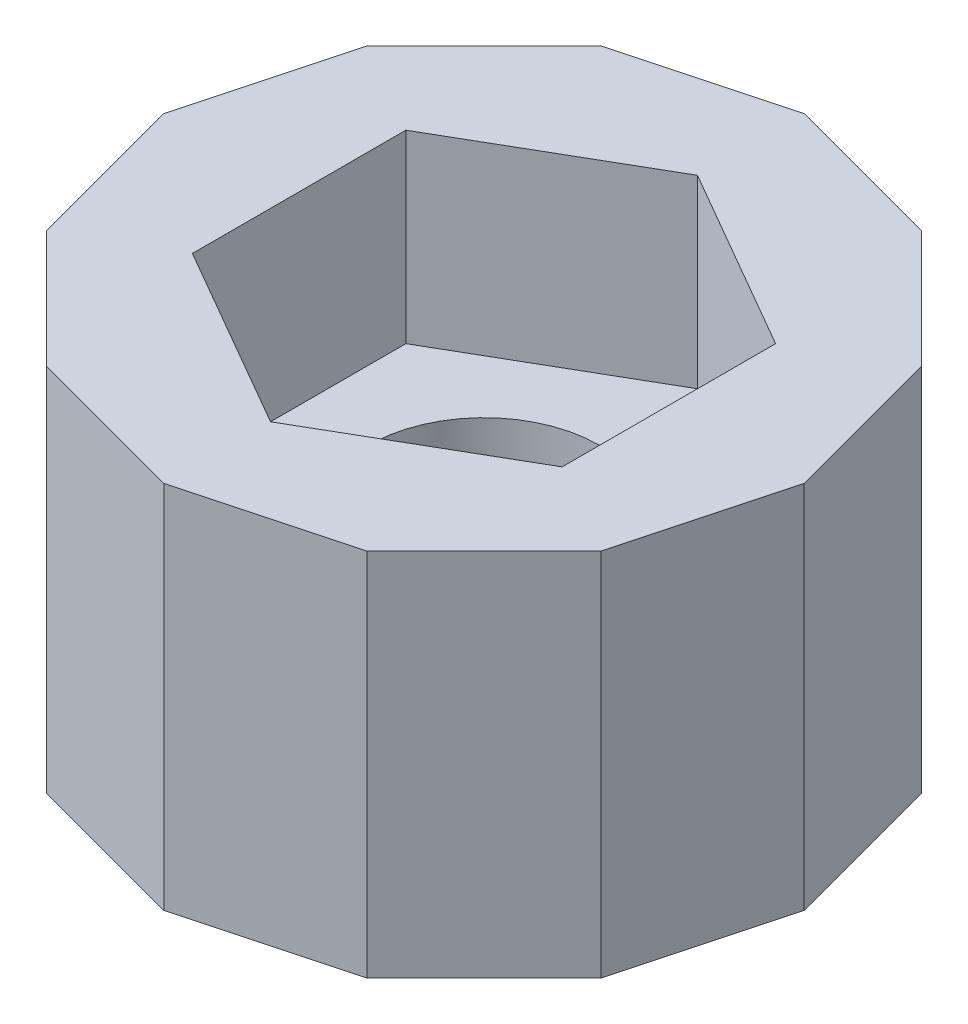
SolidWorks part; units mm, degrees
ref_plane "Plano frontal" through (0, 0, 0) normal (0, 0, 1) x (1, 0, 0)
ref_plane "Plano superior" through (0, 0, 0) normal (0, 1, 0) x (1, 0, 0)
ref_plane "Plano direito" through (0, 0, 0) normal (1, 0, 0) x (0, 0, -1)
sketch "Esboço1" plane through (0, 0, 0) normal (0, 1, 0) x (1, 0, 0)
  line L0 (0, 0) -> (0, 9.1014) construction
  line L1 (0, 0) -> (-11.8246, 0) construction
  line L3 (0, 4.6188) -> (-4, 2.3094)
  line L4 (-4, 2.3094) -> (-4, -2.3094)
  line L5 (-4, -2.3094) -> (0, -4.6188)
  line L6 (0, -4.6188) -> (4, -2.3094)
  line L7 (4, -2.3094) -> (4, 2.3094)
  line L8 (4, 2.3094) -> (0, 4.6188)
  line L9 (0, 6.9282) -> (-6, 3.4641)
  line L10 (-6, 3.4641) -> (-6, -3.4641)
  line L11 (-6, -3.4641) -> (0, -6.9282)
  line L12 (0, -6.9282) -> (6, -3.4641)
  line L13 (6, -3.4641) -> (6, 3.4641)
  line L14 (6, 3.4641) -> (0, 6.9282)
  line L15 (0, 6.9282) -> (-3.4641, 6)
  line L16 (-3.4641, 6) -> (-6, 3.4641)
  line L17 (-6, 3.4641) -> (-6.9282, 0)
  line L18 (-6.9282, 0) -> (-6, -3.4641)
  line L19 (-6, -3.4641) -> (-3.4641, -6)
  line L20 (-3.4641, -6) -> (0, -6.9282)
  line L21 (0, -6.9282) -> (3.4641, -6)
  line L22 (3.4641, -6) -> (6, -3.4641)
  line L23 (6, -3.4641) -> (6.9282, 0)
  line L24 (6.9282, 0) -> (6, 3.4641)
  line L25 (6, 3.4641) -> (3.4641, 6)
  line L26 (3.4641, 6) -> (0, 6.9282)
  circle A0 centre (0, 0) radius 2.5
  circle A1 centre (0, 0) radius 5
  circle A2 centre (0, 0) radius 4 construction
  circle A3 centre (0, 0) radius 6 construction
  circle A4 centre (0, 0) radius 6.6921 construction
  dimension "D1" = 5
  dimension "D2" = 10
extrude "Ressalto-extrusão1" add sketch "Esboço1" along normal blind 8 contours L13 L14 L9 L10 L11 L12 A1 | L15 L16 L9 | L25 L26 L14 | L23 L24 L13 | L21 L22 L12 | L19 L20 L11 | L17 L18 L10 | A1 L8 L7 L6 L5 L4 L3 region at (2.9083, 0, -5.0374) region at (3.1547, 0, -5.4641) region at (-3.1547, 0, -5.4641) region at (-6.3094, 0, 0) region at (6.3094, 0, 0) region at (-3.1547, 0, 5.4641) region at (3.1547, 0, 5.4641) region at (-4.8586, 0, 0)
extrude "Ressalto-extrusão2" add sketch "Esboço1<3>" along normal blind 4 contours L7 L8 L3 L4 L5 L6 A0 region at (1.9389, 0, -3.3583)
sketch "Esboço1<3>" plane through (0, 0, 0) normal (0, 1, 0) x (1, 0, 0) same geometry as "Esboço1"
